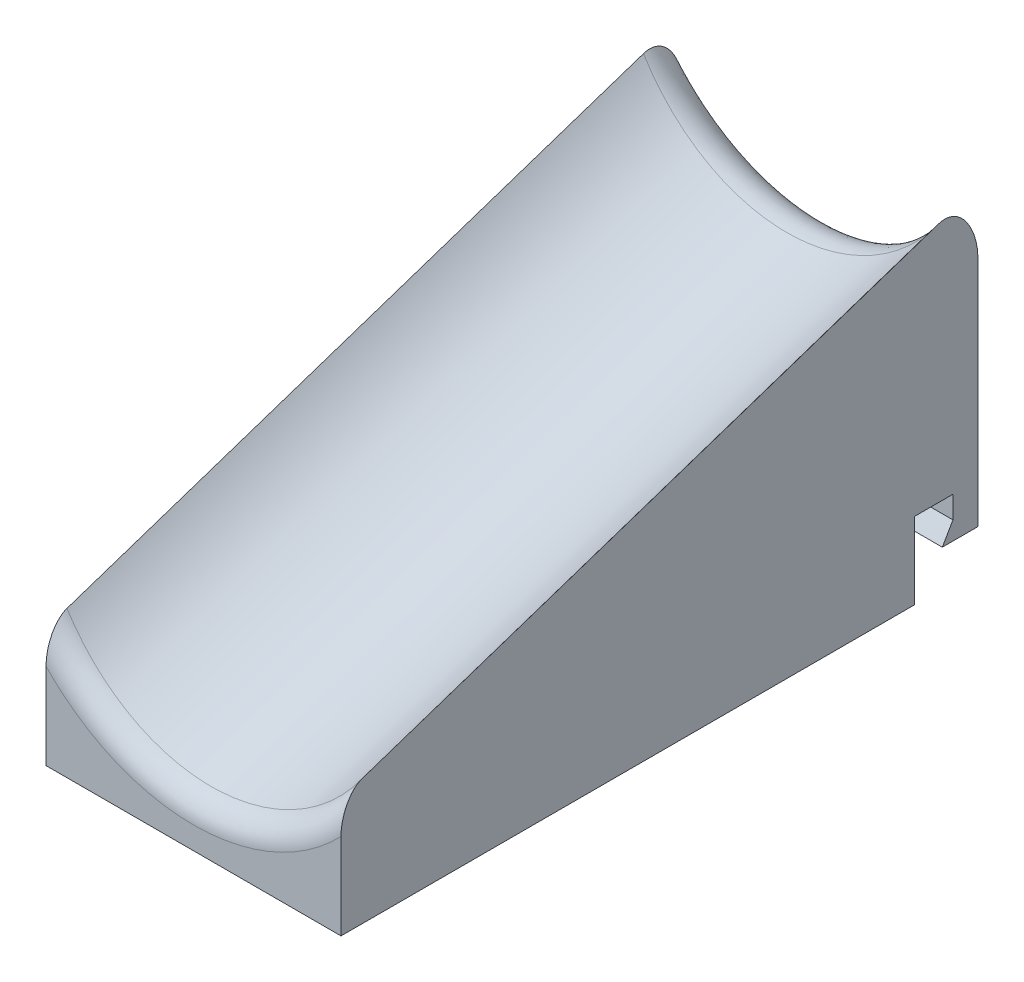
SolidWorks part; units mm, degrees
ref_plane "Front Plane" through (0, 0, 0) normal (0, 0, 1) x (1, 0, 0)
ref_plane "Top Plane" through (0, 0, 0) normal (0, 1, 0) x (1, 0, 0)
ref_plane "Right Plane" through (0, 0, 0) normal (1, 0, 0) x (0, 0, -1)
sketch "Sketch1" plane through (0, 0, 0) normal (0, 1, 0) x (1, 0, 0)
  line L1 (0, 0) -> (101.6, 0)
  line L2 (0, 0) -> (0, -304.8)
  line L3 (0, -304.8) -> (101.6, -304.8)
  line L4 (101.6, 0) -> (101.6, -304.8)
  dimension "D1" = 101.6
  dimension "D2" = 304.8
extrude "Boss-Extrude1" add sketch "Sketch1" along normal blind 101.6
sketch "Sketch3" plane through (101.6, 0, 0) normal (1, 0, 0) x (0, 0, -1)
  line L0 (-304.8, 0) -> (0, 101.6)
  line L1 (0, 101.6) -> (-304.8, 101.6)
  line L2 (-304.8, 101.6) -> (-304.8, 0)
extrude "Cut-Extrude1" cut sketch "Sketch3" against normal blind 101.6
ref_plane "Plane1" through (0, 10.16, -30.48) normal (0, 0.3162, -0.9487) x (-1, 0, 0)
sketch "Sketch4" plane through (0, 10.16, -30.48) normal (0, 0.3162, -0.9487) x (-1, 0, 0)
  line L2 (-101.6, 96.3862) -> (0, 96.3862) construction
  line L3 (0, 96.3862) -> (0, 0) construction
  circle A0 centre (-50.8, 134.4862) radius 63.5
  dimension "D1" = 127
  dimension "D2" = 38.1
  dimension "D3" = 50.8
extrude "Cut-Extrude2" cut sketch "Sketch4" against normal blind 508
sketch "Sketch7" plane through (101.6, 0, 0) normal (1, 0, 0) x (0, 0, -1)
  line L0 (-304.8, 0) -> (0, 0) construction
  line L1 (-21.79, 0) -> (-8.636, 0)
  line L2 (-21.79, 0) -> (-21.79, 13.97)
  line L3 (-21.79, 13.97) -> (-8.636, 13.97)
  line L4 (-8.636, 0) -> (-8.636, 13.97)
  line L5 (0, 101.6) -> (0, 0) construction
  dimension "D1" = 13.154
  dimension "D2" = 8.636
  dimension "D3" = 13.97
extrude "Cut-Extrude3" cut sketch "Sketch7" against normal blind 152.4
sketch "Sketch8" plane through (0, 0, 8.636) normal (0, 0, 1) x (1, 0, 0)
  line L0 (0, 0) -> (0, 13.97) construction
  line L1 (101.6, 0) -> (0, 0)
  line L2 (101.6, 0) -> (101.6, 6.985)
  line L3 (101.6, 6.985) -> (0, 6.985)
  line L4 (0, 0) -> (0, 6.985)
extrude "Boss-Extrude2" add sketch "Sketch8" along normal blind 6.35
chamfer "Chamfer1" distance 6.731 angle 60 1 edges at (50.8, 6.985, 14.986) first distance on face at (50.8, 6.985, 11.811)
sketch "Sketch9" plane through (0, 0, 0) normal (0, -1, 0) x (1, 0, 0)
  line L0 (101.6, 21.79) -> (0, 21.79)
  line L1 (101.6, 21.79) -> (101.6, 314.6167)
  line L2 (0, 21.79) -> (0, 314.6167)
  line L3 (101.6, 314.6167) -> (0, 314.6167)
  line L4 (0, 21.79) -> (101.6, 21.79) construction
extrude "Boss-Extrude3" add sketch "Sketch9" along normal blind 12.7
sketch "Sketch10" plane through (0, -12.7, 0) normal (0, -1, 0) x (-1, 0, 0)
  line L0 (-101.6, -314.6167) -> (0, -314.6167)
  line L1 (-101.6, -314.6167) -> (-101.6, -219.3667)
  line L2 (0, -314.6167) -> (0, -219.3667)
  line L3 (-101.6, -219.3667) -> (0, -219.3667)
  line L4 (-101.6, -21.79) -> (-101.6, -314.6167) construction
  line L5 (-101.6, -314.6167) -> (0, -314.6167) construction
  line L6 (0, -314.6167) -> (0, -21.79) construction
  dimension "D1" = 95.25
extrude "Cut-Extrude4" cut sketch "Sketch10" against normal blind 58.42
fillet "Fillet1" radius 8.89 1 edges at (50.8, 1.7038, 219.3667)
fillet "Fillet2" radius 11.43 1 edges at (50.8, 74.826, 0)
chamfer "Chamfer2" distance 0.3 angle 45 4 edges at (101.6, -12.7, 120.5783) (50.8, -12.7, 21.79) (0, -12.7, 120.5783) (50.8, -12.7, 219.3667)
